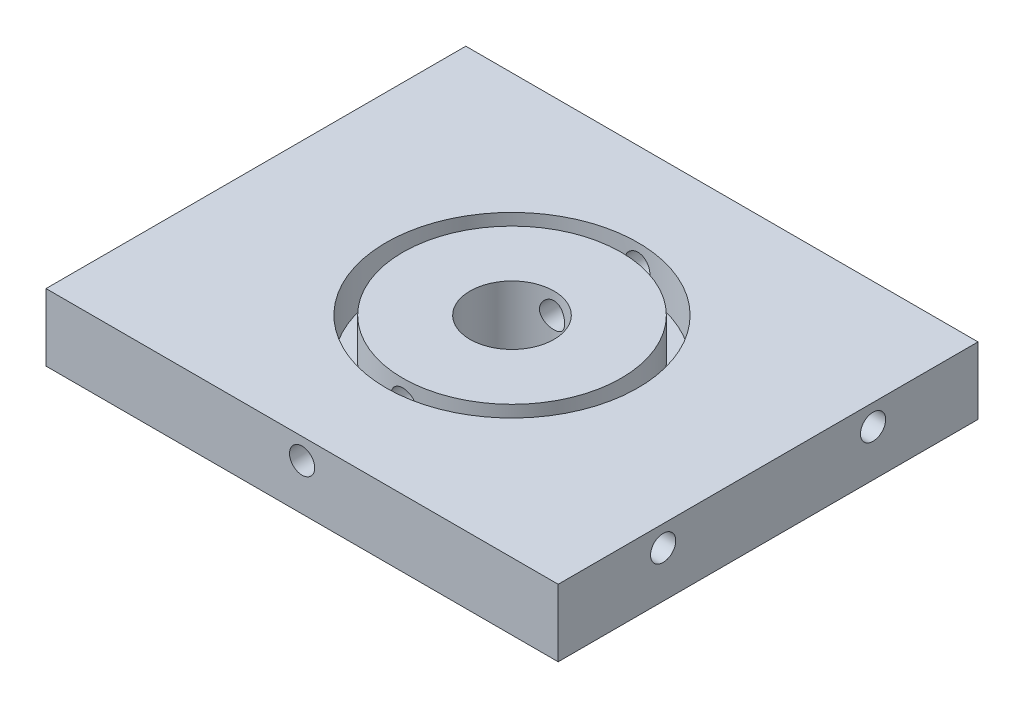
SolidWorks part; units mm, degrees
ref_plane "Plan de face" through (0, 0, 0) normal (0, 0, 1) x (1, 0, 0)
ref_plane "Plan de dessus" through (0, 0, 0) normal (0, 1, 0) x (1, 0, 0)
ref_plane "Plan de droite" through (0, 0, 0) normal (1, 0, 0) x (0, 0, -1)
sketch "Esquisse1" plane through (0, 0, 0) normal (0, 0, 1) x (1, 0, 0)
  line L0 (-5.5, -49) -> (55.5, -49) construction
  line L5 (-5.5, -45) -> (55.5, -45)
  line L6 (-5.5, -45) -> (-5.5, -53)
  line L7 (-5.5, -53) -> (55.5, -53)
  line L8 (55.5, -45) -> (55.5, -53)
  line L9 (25, -45) -> (25, -53) construction
  dimension "D1" = 8
  dimension "D2" = 61
extrude "Boss.-Extru.1" add sketch "Esquisse1" along normal blind 50 contours L5 | L7 L8 L5 L6
sketch "Esquisse2" plane through (0, -45, 0) normal (0, 1, 0) x (-1, 0, 0)
  line L0 (5.5, 50) -> (-55.5, 50) construction
  line L7 (-55.5, 50) -> (-55.5, 0) construction
  circle A0 centre (-25, 25) radius 15
  circle A2 centre (-25, 25) radius 13
  dimension "D10" = 30.5
  dimension "D11" = 25
extrude "Enlèv. mat.-Extru.1" cut sketch "Esquisse2" against normal blind 5
sketch "Esquisse3" plane through (-5.5, 0, 0) normal (-1, 0, 0) x (0, 0, 1)
  line L0 (50, -53) -> (0, -53) construction
  line L1 (0, -45) -> (0, -53) construction
  line L2 (50, -45) -> (50, -53) construction
  circle A0 centre (12.5, -47.5) radius 1.5
  circle A1 centre (37.5, -47.5) radius 1.5
  dimension "D1" = 5.5
  dimension "D2" = 5.5
  dimension "D3" = 12.5
  dimension "D4" = 12.5
extrude "Enlèv. mat.-Extru.2" cut sketch "Esquisse3" against normal blind 10
sketch "Esquisse4" plane through (55.5, 0, 0) normal (1, 0, 0) x (0, 0, -1)
  line L0 (-50, -53) -> (0, -53) construction
  line L1 (-50, -45) -> (-50, -53) construction
  line L2 (0, -45) -> (0, -53) construction
  circle A0 centre (-37.5, -47.5) radius 1.5
  circle A1 centre (-12.5, -47.5) radius 1.5
  dimension "D1" = 5.5
  dimension "D2" = 5.5
  dimension "D3" = 12.5
  dimension "D4" = 12.5
extrude "Enlèv. mat.-Extru.3" cut sketch "Esquisse4" against normal blind 10
sketch "Esquisse5" plane through (0, 0, 0) normal (0, 0, -1) x (-1, 0, 0)
  line L0 (5.5, -45) -> (-55.5, -45) construction
  line L1 (-55.5, -45) -> (-55.5, -53) construction
  circle A0 centre (-25, -47.5) radius 1.5
  dimension "D1" = 2.5
  dimension "D2" = 30.5
extrude "Enlèv. mat.-Extru.4" cut sketch "Esquisse5" against normal through all
sketch "Esquisse6" plane through (0, -45, 0) normal (0, 1, 0) x (1, 0, 0)
  line L0 (-5.5, -50) -> (-5.5, 0) construction
  line L1 (-5.5, -50) -> (55.5, -50) construction
  circle A0 centre (25, -25) radius 5
  dimension "D1" = 30.5
  dimension "D2" = 25
extrude "Enlèv. mat.-Extru.5" cut sketch "Esquisse6" against normal through all contours A0
